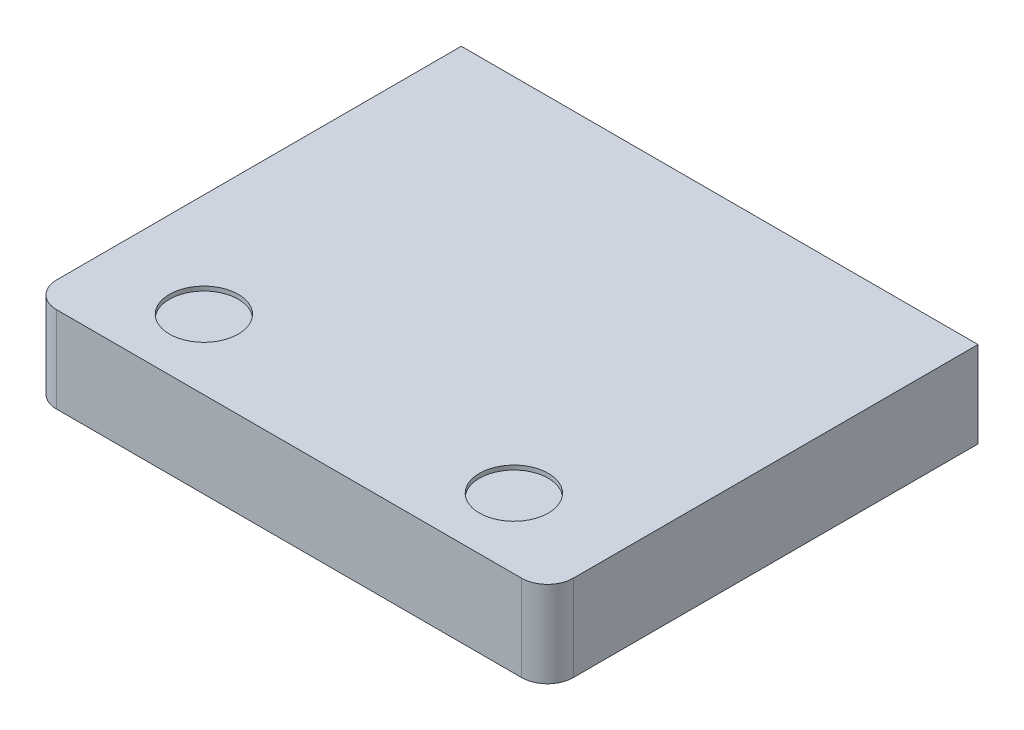
SolidWorks part; units mm, degrees
ref_plane "前视基准面" through (0, 0, 0) normal (0, 0, 1) x (1, 0, 0)
ref_plane "上视基准面" through (0, 0, 0) normal (0, 1, 0) x (1, 0, 0)
ref_plane "右视基准面" through (0, 0, 0) normal (1, 0, 0) x (0, 0, -1)
sketch "草图1" plane through (0, 0, 0) normal (0, 1, 0) x (1, 0, 0)
  line L1 (-30, 25) -> (30, 25)
  line L2 (-30, 25) -> (-30, -25)
  line L3 (-30, -25) -> (30, -25)
  line L4 (30, 25) -> (30, -25)
  line L5 (-30, 25) -> (30, -25) construction
  line L6 (-30, -25) -> (30, 25) construction
  point P0 (0, 0)
  dimension "D1" = 60
  dimension "D2" = 50
extrude "凸台-拉伸1" add sketch "草图1" along normal blind 10
fillet "圆角1" radius 3 2 edges at (-30, 5, 25) (30, 5, 25)
sketch "草图2" plane through (0, 10, 0) normal (0, 1, 0) x (1, 0, 0)
  line L0 (0, 0) -> (0, -25) construction
  line L1 (-27, -25) -> (27, -25) construction
  circle A0 centre (-18, -16.9) radius 4
  circle A1 centre (18, -16.9) radius 4
  dimension "D1" = 8
  dimension "D2" = 36
  dimension "D3" = 8.1
extrude "切除-拉伸1" cut sketch "草图2" against normal blind 0.5 contours A1 | A0
